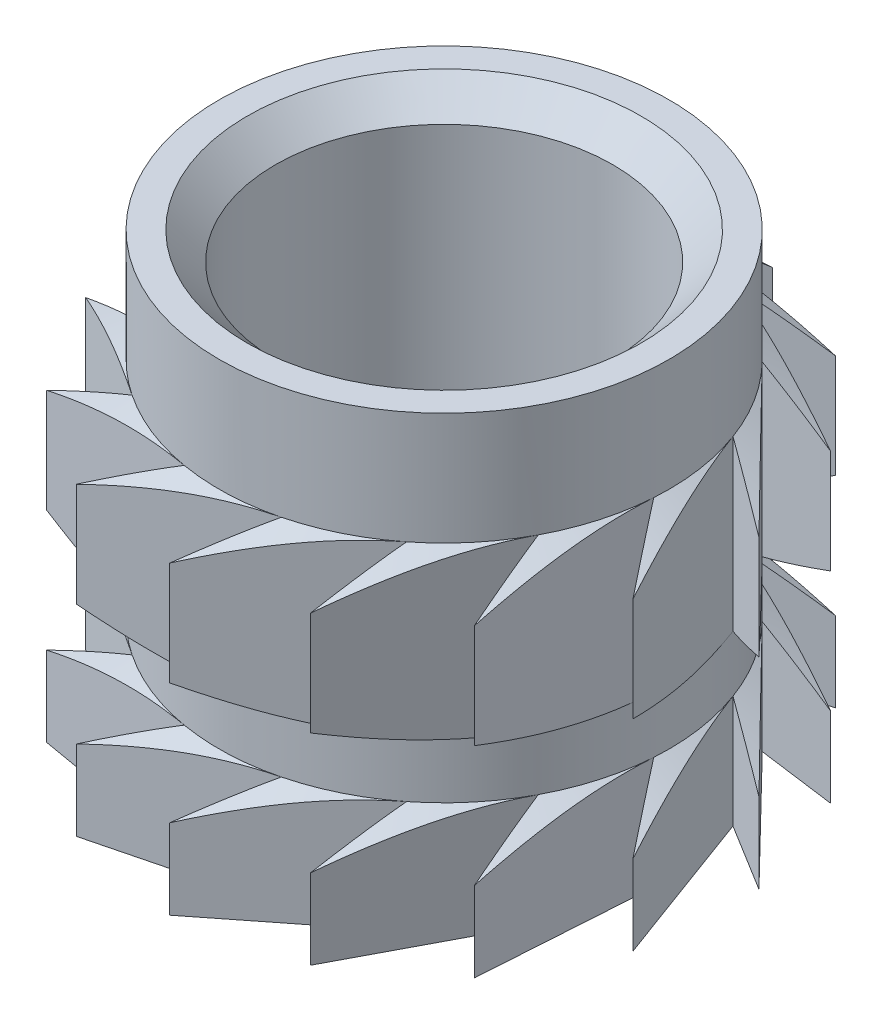
SolidWorks part; units mm, degrees
ref_plane "Front Plane" through (0, 0, 0) normal (0, 0, 1) x (1, 0, 0)
ref_plane "Top Plane" through (0, 0, 0) normal (0, 1, 0) x (1, 0, 0)
ref_plane "Right Plane" through (0, 0, 0) normal (1, 0, 0) x (0, 0, -1)
sketch "Sketch1" plane through (0, 0, 0) normal (0, 1, 0) x (1, 0, 0)
  circle A0 centre (0, 0) radius 1.5
  circle A1 centre (0, 0) radius 2
  dimension "D1" = 3
  dimension "D2" = 4
extrude "Boss-Extrude1" add sketch "Sketch1" along normal blind 4
sketch "Sketch2" plane through (0, 0, 0) normal (0, 0, 1) x (1, 0, 0)
  line L0 (-2, 0) -> (2, 0) construction
  line L1 (-2, 4) -> (-2, 0) construction
  line L2 (2, 4) -> (-2, 4) construction
  line L3 (2, 0) -> (2, 4) construction
  line L4 (-2, 0) -> (2, 0) construction
  line L5 (-2, 4) -> (-2, 0) construction
  line L6 (2, 4) -> (-2, 4) construction
  line L7 (2, 0) -> (2, 4) construction
  line L8 (2, 3) -> (2.5, 2.7113)
  line L9 (2.5, 2.7113) -> (2.5, 1.7887)
  line L10 (2.5, 1.7887) -> (2, 1.5)
  line L11 (2, 0) -> (2.5, 0)
  line L12 (2.5, 0) -> (2.5, 0.7113)
  line L13 (2.5, 0.7113) -> (2, 1)
  line L14 (2, 1) -> (2, 0)
  line L15 (2, 1.5) -> (2, 3)
  line L16 (0, 0) -> (0, 50000) construction
  dimension "D1" = 1
  dimension "D2" = 1.5
  dimension "D3" = 1
  dimension "D4" = 0.5
  dimension "D5" = 60
  dimension "D6" = 60
  dimension "D7" = 60
revolve "Revolve1" add sketch "Sketch2" angle 360 about L16
sketch "Sketch3" plane through (0, 4, 0) normal (0, 1, 0) x (1, 0, 0)
  line L0 (-0.0773, 1.9985) -> (1.4216, 2.0565)
  line L1 (1.4216, 2.0565) -> (0.7422, 1.8572)
  line L2 (0.7422, 1.8572) -> (2.1351, 1.3005)
  line L3 (2.1351, 1.3005) -> (1.4335, 1.3947)
  line L4 (1.4335, 1.3947) -> (2.4795, 0.3196)
  line L5 (2.4795, 0.3196) -> (1.8768, 0.6911)
  line L6 (1.8768, 0.6911) -> (2.3951, -0.7165)
  line L7 (2.3951, -0.7165) -> (1.9956, -0.132)
  line L8 (1.9956, -0.132) -> (1.8966, -1.6288)
  line L9 (1.8966, -1.6288) -> (1.7694, -0.9323)
  line L10 (1.7694, -0.9323) -> (1.0702, -2.2594)
  line L11 (1.0702, -2.2594) -> (1.2372, -1.5714)
  line L12 (1.2372, -1.5714) -> (0.0587, -2.4993)
  line L13 (0.0587, -2.4993) -> (0.4911, -1.9388)
  line L14 (0.4911, -1.9388) -> (-0.9629, -2.3071)
  line L15 (-0.9629, -2.3071) -> (-0.3399, -1.9709)
  line L16 (-0.3399, -1.9709) -> (-1.8181, -1.716)
  line L17 (-1.8181, -1.716) -> (-1.1122, -1.6623)
  line L18 (-1.1122, -1.6623) -> (-2.3589, -0.8281)
  line L19 (-2.3589, -0.8281) -> (-1.6921, -1.0662)
  line L20 (-1.6921, -1.0662) -> (-2.4918, 0.2029)
  line L21 (-2.4918, 0.2029) -> (-1.9795, -0.2858)
  line L22 (-1.9795, -0.2858) -> (-2.1938, 1.1988)
  line L23 (-2.1938, 1.1988) -> (-1.9246, 0.5441)
  line L24 (-1.9246, 0.5441) -> (-1.5165, 1.9875)
  line L25 (-1.5165, 1.9875) -> (-1.5369, 1.2798)
  line L26 (-1.5369, 1.2798) -> (-0.577, 2.4325)
  line L27 (-0.577, 2.4325) -> (-0.8835, 1.7943)
  line L28 (-0.8835, 1.7943) -> (0.4622, 2.4569)
  line L29 (0.4622, 2.4569) -> (-0.0773, 1.9985)
  circle A0 centre (0, 0) radius 2 construction
  circle A1 centre (0, 0) radius 2 construction
  circle A2 centre (0, 0) radius 2.5 construction
  arc A3 (-0.0773, 1.9985) -> (0.7422, 1.8572) centre (0, 0) cw
  arc A4 (0.7422, 1.8572) -> (1.4335, 1.3947) centre (0, 0) cw
  arc A5 (1.4335, 1.3947) -> (1.8768, 0.6911) centre (0, 0) cw
  arc A6 (1.8768, 0.6911) -> (1.9956, -0.132) centre (0, 0) cw
  arc A7 (1.9956, -0.132) -> (1.7694, -0.9323) centre (0, 0) cw
  arc A8 (1.7694, -0.9323) -> (1.2372, -1.5714) centre (0, 0) cw
  arc A9 (1.2372, -1.5714) -> (0.4911, -1.9388) centre (0, 0) cw
  arc A10 (0.4911, -1.9388) -> (-0.3399, -1.9709) centre (0, 0) cw
  arc A11 (-0.3399, -1.9709) -> (-1.1122, -1.6623) centre (0, 0) cw
  arc A12 (-1.1122, -1.6623) -> (-1.6921, -1.0662) centre (0, 0) cw
  arc A13 (-1.6921, -1.0662) -> (-1.9795, -0.2858) centre (0, 0) cw
  arc A14 (-1.9795, -0.2858) -> (-1.9246, 0.5441) centre (0, 0) cw
  arc A15 (-1.9246, 0.5441) -> (-1.5369, 1.2798) centre (0, 0) cw
  arc A16 (-1.5369, 1.2798) -> (-0.8835, 1.7943) centre (0, 0) cw
  arc A17 (-0.8835, 1.7943) -> (-0.0773, 1.9985) centre (0, 0) cw
  circle A18 centre (0, 0) radius 2.5
  circle A19 centre (0, 0) radius 2 construction
  point P8 (0, 2)
  point P10 (0, 0)
  point P53 (0, 0)
  point P56 (-0.577, 2.4325)
  dimension "D1" = 15
extrude "Cut-Extrude3" cut sketch "Sketch3" against normal through all contours L28 A18 L27 | L0 A18 L29 | L2 A18 L1 | L4 A18 L3 | L6 A18 L5 | L8 A18 L7 | L10 A18 L9 | L12 A18 L11 | L14 A18 L13 | L16 A18 L15 | L18 A18 L17 | L20 A18 L19 | L22 A18 L21 | L24 A18 L23 | L26 A18 L25 region at (0.6383, 4, -2.1816) region at (1.4705, 4, -1.7334) region at (-0.3043, 4, -2.2526) region at (2.0484, 4, -0.9855) region at (-1.1942, 4, -1.9341) region at (2.2721, 4, -0.0671) region at (-1.8776, 4, -1.2812) region at (-2.2364, 4, -0.4067) region at (2.103, 4, 0.8628) region at (-2.2085, 4, 0.5381) region at (1.5702, 4, 1.6436) region at (-1.7987, 4, 1.3898) region at (0.766, 4, 2.1402) region at (-1.0779, 4, 2.0013) region at (-0.1707, 4, 2.2667)
chamfer "Chamfer1" distance 0.25 angle 45 2 edges at (0, 4, 1.5) (0, 0, 1.5)
